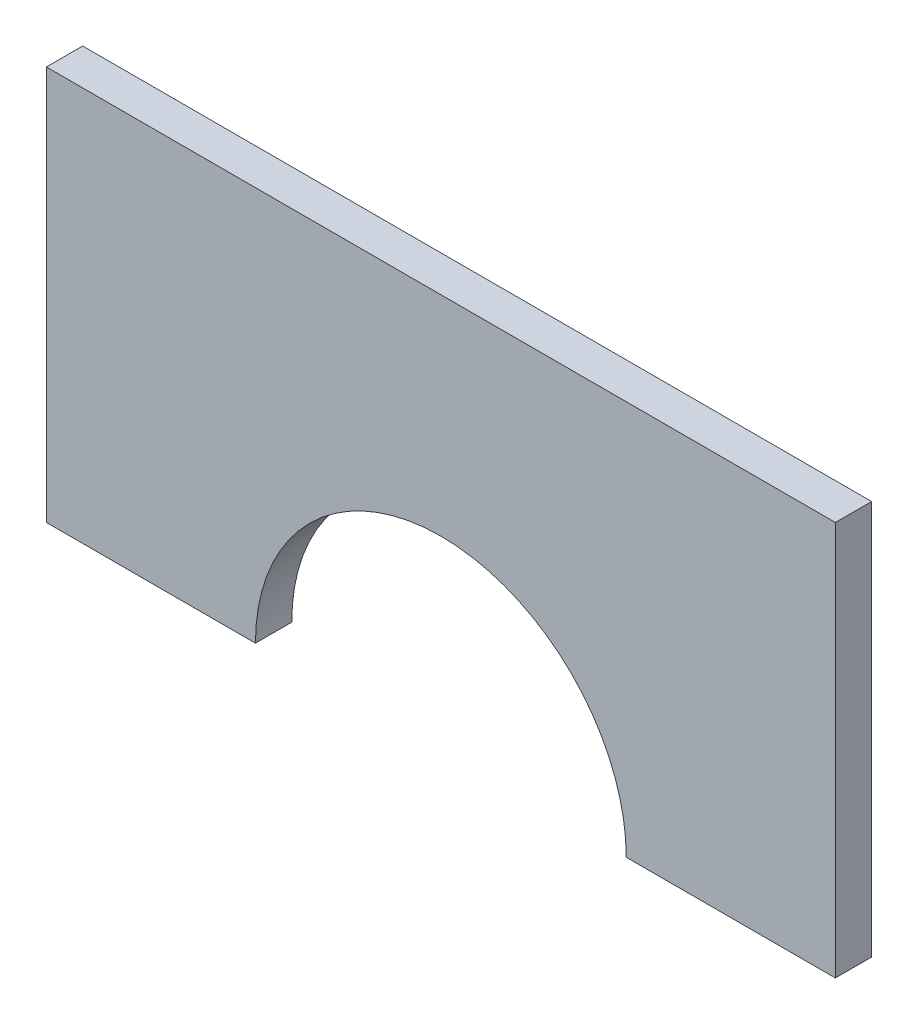
SolidWorks part; units mm, degrees
ref_plane "Plan de face" through (0, 0, 0) normal (0, 0, 1) x (1, 0, 0)
ref_plane "Plan de dessus" through (0, 0, 0) normal (0, 1, 0) x (1, 0, 0)
ref_plane "Plan de droite" through (0, 0, 0) normal (1, 0, 0) x (0, 0, -1)
sketch "Esquisse1" plane through (0, 0, 0) normal (0, 0, 1) x (1, 0, 0)
  line L1 (-44.1717, 36.1501) -> (55.8283, 36.1501)
  line L2 (-44.1717, 36.1501) -> (-44.1717, -13.8499)
  line L3 (-44.1717, -13.8499) -> (55.8283, -13.8499)
  line L4 (55.8283, 36.1501) -> (55.8283, -13.8499)
  arc A0 (29.3283, -13.8499) -> (-17.6717, -13.8499) centre (5.8283, -13.8499) ccw
  dimension "D1" = 23.5
  dimension "D2" = 100
  dimension "D3" = 50
extrude "Boss.-Extru.1" add sketch "Esquisse1" along normal blind 4.6 contours A0 L3 L4 L1 L2 region at (5.8283, 14.3043, 0)
